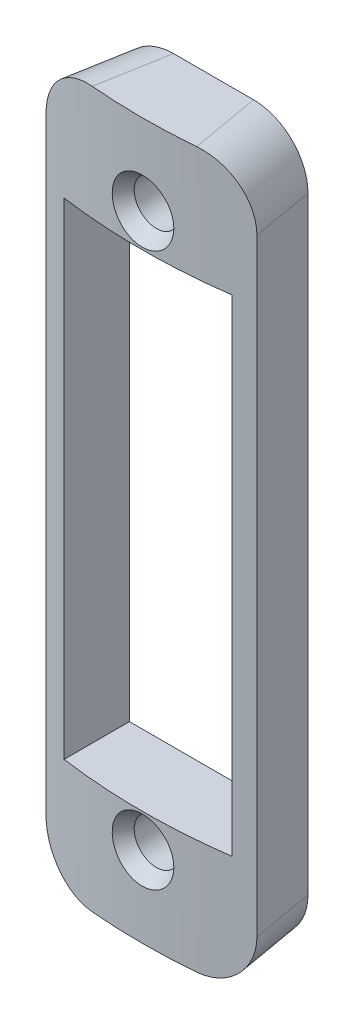
SolidWorks part; units mm, degrees
material "ABS"
ref_plane "Front Plane" through (0, 0, 0) normal (0, 0, 1) x (1, 0, 0)
ref_plane "Top Plane" through (0, 0, 0) normal (0, 1, 0) x (1, 0, 0)
ref_plane "Right Plane" through (0, 0, 0) normal (1, 0, 0) x (0, 0, -1)
sketch "Sketch1" plane through (0, 0, 0) normal (1, 0, 0) x (0, 0, -1)
  line L0 (33.9725, 0) -> (33.9725, 16.293) construction
  line L2 (0, 0) -> (2, 0)
  line L3 (0, 0) -> (0, 40)
  line L4 (0, 40) -> (2, 40)
  line L5 (2, 0) -> (2, 40)
  dimension "D1" = 33.9725
  dimension "D2" = 2
  dimension "D3" = 40
revolve "BULK EXTRUDE" add sketch "Sketch1" angle 20 mid plane about L0
sketch "Sketch2" plane through (0, 0, 0) normal (0, 0, 1) x (1, 0, 0)
  line L0 (0, 0) -> (0, 6.4) construction
  line L1 (-4.7, 33.6) -> (4.7, 33.6)
  line L2 (-4.7, 33.6) -> (-4.7, 6.4)
  line L3 (-4.7, 6.4) -> (4.7, 6.4)
  line L4 (4.7, 33.6) -> (4.7, 6.4)
  line L5 (0, 33.6) -> (0, 35.48) construction
  line L6 (0, 6.4) -> (0, 4.52) construction
  circle A0 centre (0, 4.52) radius 1.25
  circle A1 centre (0, 35.48) radius 1.25
  point P7 (-4.7, 20)
  dimension "D4" = 2.5
  dimension "D1" = 27.2
  dimension "D2" = 9.4
  dimension "D3" = 20
  dimension "D5" = 30.96
extrude "CONNECTOR PASSTHRU" cut sketch "Sketch2" against normal through all both and the other way through all
ref_plane "REAR FLATTENING PLANE" through (0, 0, -2.4857) normal (0, 0, 1) x (1, 0, 0)
sketch "Sketch3" plane through (0, 0, -2.4857) normal (0, 0, 1) x (1, 0, 0)
  line L0 (4.7, 6.4) -> (4.7, 33.6) construction
  line L1 (4.7, 6.4) -> (-4.7, 6.4) construction
  line L2 (-4.7, 33.6) -> (-4.7, 6.4) construction
  line L3 (-4.7, 33.6) -> (4.7, 33.6) construction
  line L4 (-5.552, 0) -> (5.552, 0)
  line L5 (-5.552, 40) -> (-5.552, 0)
  line L6 (5.552, 40) -> (-5.552, 40)
  line L7 (5.552, 0) -> (5.552, 40)
  line L8 (-5.552, 0) -> (5.552, 0)
  line L9 (-5.552, 40) -> (-5.552, 0)
  line L10 (5.552, 40) -> (-5.552, 40)
  line L11 (5.552, 0) -> (5.552, 40)
  line L12 (4.7, 6.4) -> (4.7, 33.6)
  line L13 (4.7, 6.4) -> (-4.7, 6.4)
  line L14 (-4.7, 33.6) -> (-4.7, 6.4)
  line L15 (-4.7, 33.6) -> (4.7, 33.6)
  circle A0 centre (0, 4.52) radius 1.25 construction
  circle A1 centre (0, 35.48) radius 1.25 construction
  circle A2 centre (0, 4.52) radius 1.25
  circle A3 centre (0, 35.48) radius 1.25
  dimension "D1" = 0
extrude "REAR FLATTENING" add sketch "Sketch3" along normal up to next and the other way blind 1.5
sketch "Sketch4" plane through (5.8096, 0, -1.0244) normal (0.9848, 0, -0.1736) x (-0.1736, 0, -0.9848)
  line L1 (-0.5161, 40) -> (4.8893, 40)
  line L2 (-0.5161, 40) -> (-0.5161, 0)
  line L3 (-0.5161, 0) -> (4.8893, 0)
  line L4 (4.8893, 40) -> (4.8893, 0)
extrude "Cut-Extrude2" cut sketch "Sketch4" along normal through all
sketch "Sketch5" plane through (-5.8096, 0, -1.0244) normal (-0.9848, 0, -0.1736) x (-0.1736, 0, 0.9848)
  line L1 (0.5161, 40) -> (-4.8433, 40)
  line L2 (0.5161, 40) -> (0.5161, 0)
  line L3 (0.5161, 0) -> (-4.8433, 0)
  line L4 (-4.8433, 40) -> (-4.8433, 0)
extrude "Cut-Extrude3" cut sketch "Sketch5" along normal through all
fillet "Fillet1" radius 3 4 edges at (5.5934, 40, -2.2509) (5.5934, 0, -2.2509) (-5.5934, 0, -2.2509) (-5.5934, 40, -2.2509)
ref_axis "Axis1" through (0, 4.52, -3.9857) along (0, 0, 1)
ref_plane "Plane1" through (0, 0, 0) normal (-1, 0, 0) x (0, 0, 1)
sketch "Sketch6" plane through (0, 0, 0) normal (-1, 0, 0) x (0, 0, 1)
  line L0 (0, 4.52) -> (0, 6.27)
  line L1 (-3.9857, 4.52) -> (0, 4.52) construction
  line L2 (0, 6.27) -> (-1, 5.645)
  line L3 (-1, 5.645) -> (-1, 4.52)
  line L4 (-1, 4.52) -> (0, 4.52)
  dimension "D1" = 1
  dimension "D2" = 1.75
  dimension "D3" = 1.125
revolve "Cut-Revolve1" cut sketch "Sketch6" angle 360 about axis through (0, 4.52, -3.9857) along (0, 0, 1)
ref_plane "Plane2" through (0, 20, 0) normal (0, 1, 0) x (1, 0, 0)
mirror "Mirror1" about plane through (0, 20, 0) normal (0, 1, 0) of "Cut-Revolve1"
